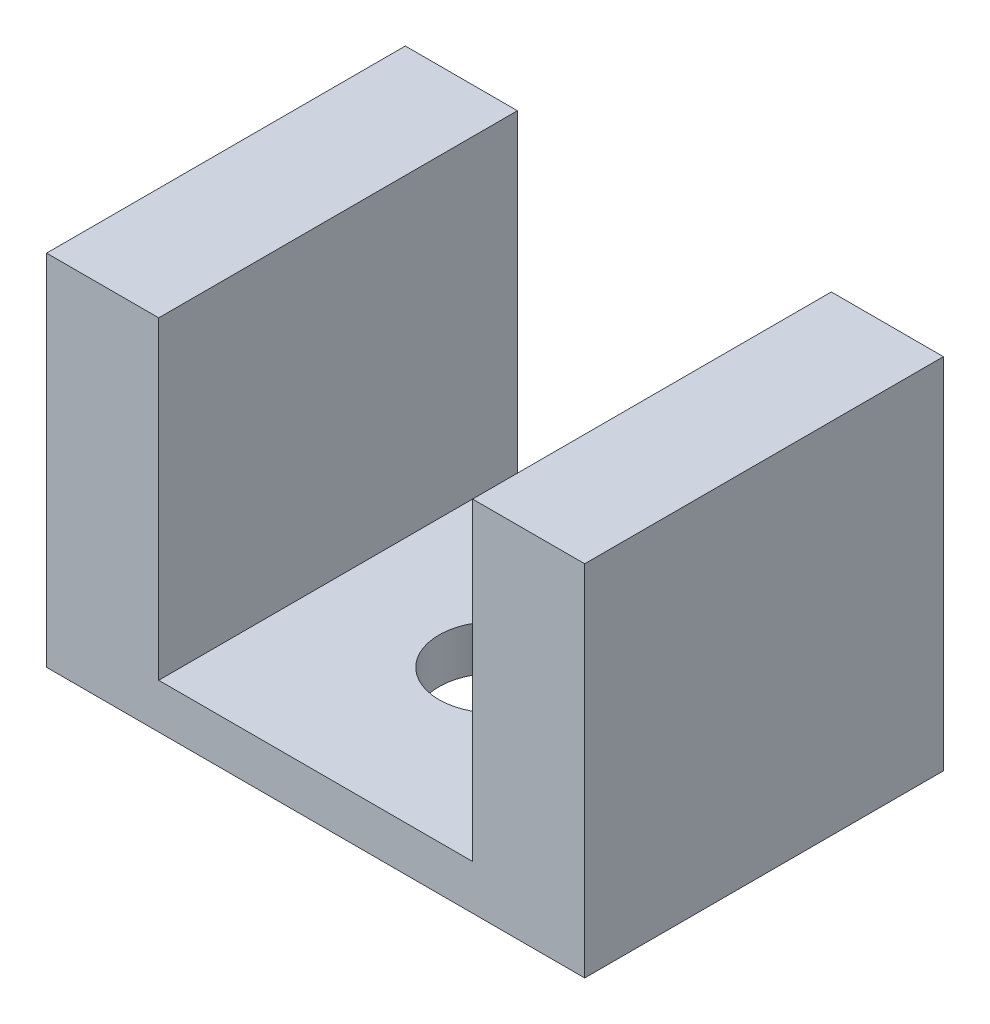
SolidWorks part; units mm, degrees
material "6063-O"
ref_plane "Front" through (0, 0, 0) normal (0, 0, 1) x (1, 0, 0)
ref_plane "Top" through (0, 0, 0) normal (0, 1, 0) x (1, 0, 0)
ref_plane "Right" through (0, 0, 0) normal (1, 0, 0) x (0, 0, -1)
sketch "Sketch1" plane through (0, 0, 0) normal (0, 0, 1) x (1, 0, 0)
  line L0 (0, 0) -> (0, 61400.5293) construction
  line L1 (22.225, 0) -> (-22.225, 0)
  line L2 (-22.225, 0) -> (-22.225, 44.45)
  line L3 (-22.225, 44.45) -> (-38.1, 44.45)
  line L4 (-38.1, 44.45) -> (-38.1, -6.35)
  line L5 (-38.1, -6.35) -> (38.1, -6.35)
  line L6 (38.1, 44.45) -> (38.1, -6.35)
  line L7 (22.225, 0) -> (22.225, 44.45)
  line L8 (22.225, 44.45) -> (38.1, 44.45)
  point P5 (-27.5828, 0)
  point P10 (-27.3844, 0)
  point P11 (-38.6953, -11.2117)
  point P13 (0, 0)
  point P14 (0, -6.35)
  dimension "D1" = 15.875
  dimension "D2" = 50.8
  dimension "D3" = 6.35
  dimension "D4" = 38.1
extrude "Boss-Extrude1" add sketch "Sketch1" along normal blind 50.8
sketch "Sketch2" plane through (0, 0, 0) normal (0, 1, 0) x (1, 0, 0)
  line L0 (0, 0) -> (0, -50.8) construction
  line L1 (22.225, -50.8) -> (-22.225, -50.8) construction
  circle A0 centre (0, -25.4) radius 7.9375
  dimension "D1" = 15.875
extrude "Cut-Extrude1" cut sketch "Sketch2" against normal through all
